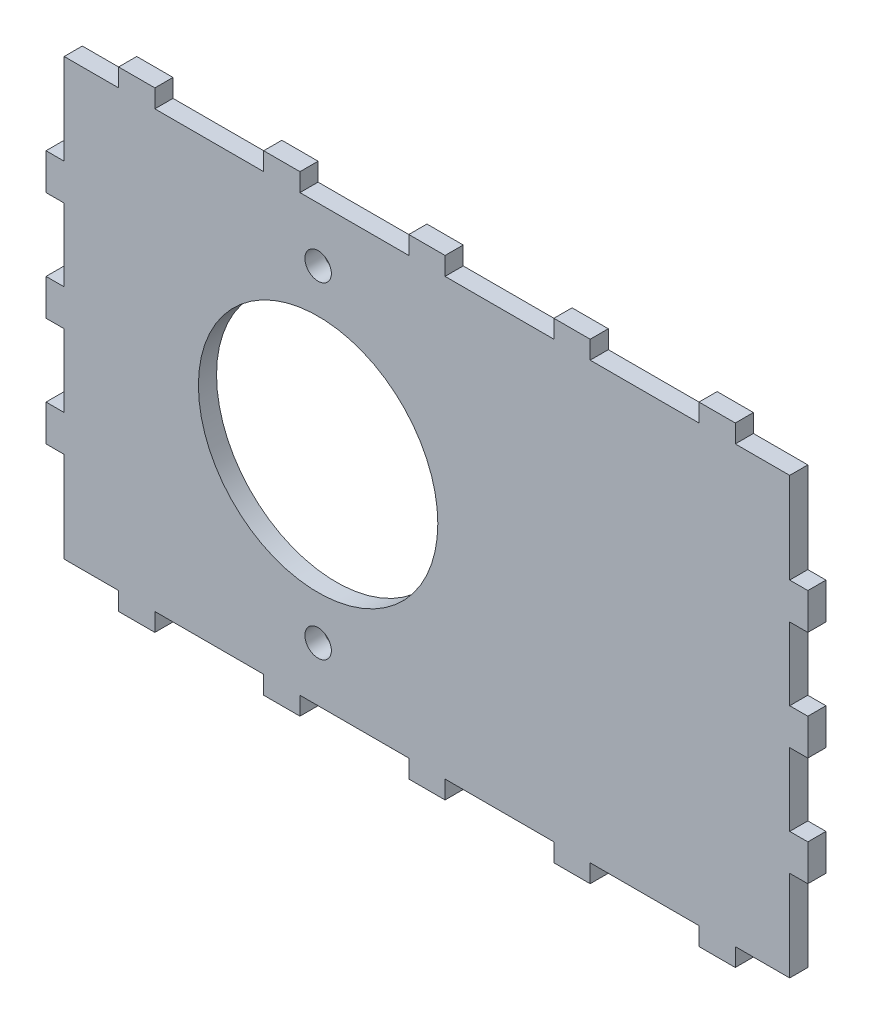
SolidWorks part; units mm, degrees
ref_plane "Ön Düzlem" through (0, 0, 0) normal (0, 0, 1) x (1, 0, 0)
ref_plane "Üst Düzlem" through (0, 0, 0) normal (0, 1, 0) x (1, 0, 0)
ref_plane "Sağ Düzlem" through (0, 0, 0) normal (1, 0, 0) x (0, 0, -1)
sketch "Sketch1" plane through (0, 0, 0) normal (0, 0, 1) x (1, 0, 0)
  line L0 (-85, 60) -> (-85, 65)
  line L1 (-100, -60) -> (-85, -60)
  line L2 (-100, -60) -> (-100, -35)
  line L3 (-100, 60) -> (-85, 60)
  line L4 (100, -60) -> (100, -35)
  line L5 (-100, -60) -> (100, 60) construction
  line L6 (-100, 60) -> (100, -60) construction
  line L7 (-85, 65) -> (-75, 65)
  line L8 (-75, 65) -> (-75, 60)
  line L9 (-45, 60) -> (-45, 65)
  line L10 (-35, 65) -> (-35, 60)
  line L11 (-45, 65) -> (-35, 65)
  line L12 (-5, 60) -> (-5, 65)
  line L13 (5, 65) -> (5, 60)
  line L14 (-5, 65) -> (5, 65)
  line L15 (35, 60) -> (35, 65)
  line L16 (45, 65) -> (45, 60)
  line L17 (35, 65) -> (45, 65)
  line L18 (75, 60) -> (75, 65)
  line L19 (85, 65) -> (85, 60)
  line L20 (75, 65) -> (85, 65)
  line L21 (-75, 60) -> (-45, 60)
  line L22 (-35, 60) -> (-5, 60)
  line L23 (5, 60) -> (35, 60)
  line L24 (45, 60) -> (75, 60)
  line L25 (85, 60) -> (100, 60)
  line L26 (-105, 0) -> (105, 0) construction
  line L27 (0, -60) -> (0, 60) construction
  line L28 (-100, 35) -> (-105, 35)
  line L29 (-105, 35) -> (-105, 25)
  line L30 (-105, 25) -> (-100, 25)
  line L31 (-105, -5) -> (-100, -5)
  line L32 (-100, 5) -> (-105, 5)
  line L33 (-105, 5) -> (-105, -5)
  line L34 (-105, -35) -> (-100, -35)
  line L35 (-100, -25) -> (-105, -25)
  line L36 (-105, -25) -> (-105, -35)
  line L37 (105, 25) -> (100, 25)
  line L38 (100, 35) -> (105, 35)
  line L39 (105, 35) -> (105, 25)
  line L40 (100, 5) -> (105, 5)
  line L41 (105, 5) -> (105, -5)
  line L42 (105, -5) -> (100, -5)
  line L43 (100, -25) -> (105, -25)
  line L44 (105, -25) -> (105, -35)
  line L45 (105, -35) -> (100, -35)
  line L46 (85, -65) -> (85, -60)
  line L47 (75, -65) -> (85, -65)
  line L48 (75, -60) -> (75, -65)
  line L49 (45, -65) -> (45, -60)
  line L50 (35, -65) -> (45, -65)
  line L51 (35, -60) -> (35, -65)
  line L52 (5, -65) -> (5, -60)
  line L53 (-5, -65) -> (5, -65)
  line L55 (-35, -65) -> (-35, -60)
  line L56 (-45, -65) -> (-35, -65)
  line L57 (-45, -60) -> (-45, -65)
  line L58 (-75, -65) -> (-75, -60)
  line L59 (-85, -65) -> (-75, -65)
  line L60 (-85, -60) -> (-85, -65)
  line L61 (-75, -60) -> (-45, -60)
  line L63 (5, -60) -> (35, -60)
  line L64 (45, -60) -> (75, -60)
  line L65 (85, -60) -> (100, -60)
  line L66 (-100, -25) -> (-100, -5)
  line L67 (-100, 5) -> (-100, 25)
  line L68 (-100, 35) -> (-100, 60)
  line L69 (100, 35) -> (100, 60)
  line L70 (100, 5) -> (100, 25)
  line L71 (100, -25) -> (100, -5)
  line L72 (-35, -60) -> (-5, -60)
  line L73 (-5, -60) -> (-5, -65)
  circle A0 centre (-30, 0) radius 33
  circle A1 centre (-30, 0) radius 45 construction
  circle A2 centre (-30, -45) radius 3.65
  circle A3 centre (-30, 45) radius 3.65
  point P0 (0, 0)
  point P78 (0, 0)
  dimension "D3" = 66
  dimension "D5" = 90
  dimension "D6" = 7.3
  dimension "D1" = 120
  dimension "D2" = 200
  dimension "D4" = 30
  dimension "D7" = 10
  dimension "D8" = 5
  dimension "D9" = 15
  dimension "D11" = 30
  dimension "D12" = 5
  dimension "D13" = 10
  dimension "D14" = 25
  dimension "D16" = 30
  dimension "D17" = 20
  dimension "D18" = 30
  dimension "D10" = 5
  dimension "D15" = 3
extrude "Boss-Extrude1" add sketch "Sketch1" along normal blind 5
